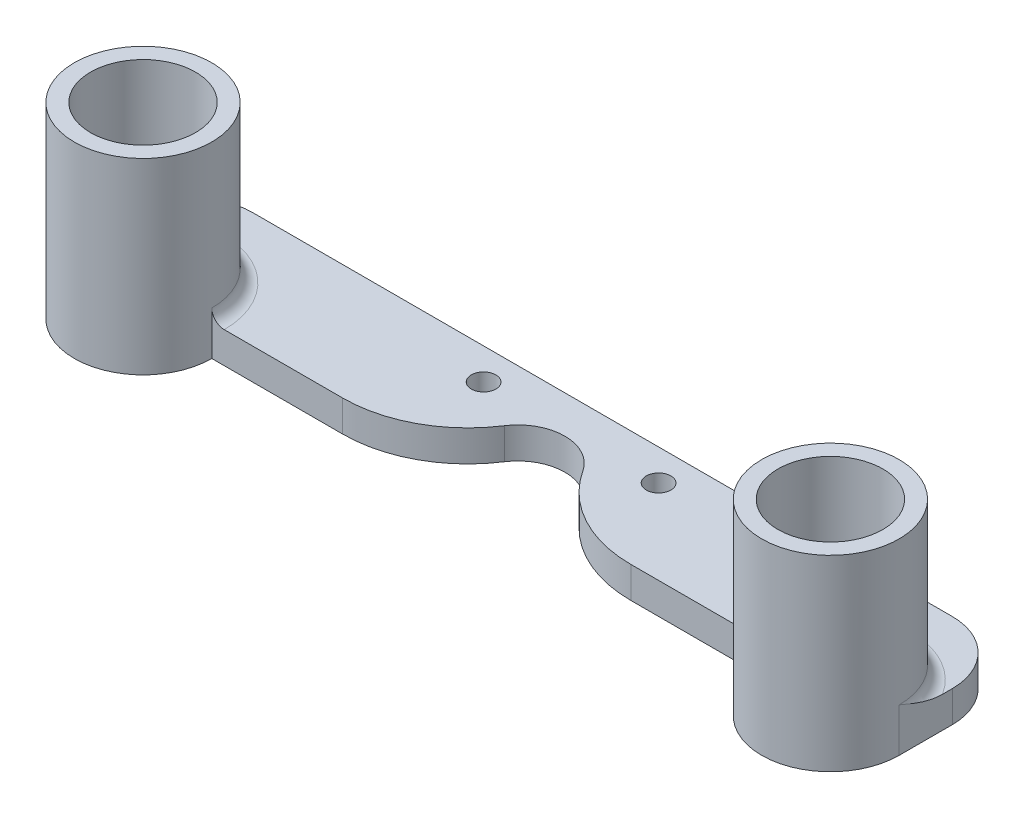
SolidWorks part; units mm, degrees
ref_plane "Front Plane" through (0, 0, 0) normal (0, 0, 1) x (1, 0, 0)
ref_plane "Top Plane" through (0, 0, 0) normal (0, 1, 0) x (1, 0, 0)
ref_plane "Right Plane" through (0, 0, 0) normal (1, 0, 0) x (0, 0, -1)
sketch "Sketch1" plane through (0, 0, 0) normal (0, 1, 0) x (1, 0, 0)
  line L0 (0, 0) -> (30.6893, 0) construction
  line L1 (30.6893, 0) -> (0, 0) construction
  line L2 (0, 0) -> (-18.0912, 0) construction
  line L3 (-81.0707, 0) -> (-54.4628, 0)
  line L5 (-109.0107, 0) -> (-109.0107, 10.795)
  line L6 (-96.3107, 23.495) -> (45.9293, 23.495)
  line L7 (58.6293, 0) -> (58.6293, 10.795)
  line L8 (4.0813, 0) -> (30.6893, 0)
  line L9 (-32.2902, 0) -> (-81.0707, 0) construction
  arc A0 (-109.0107, 0) -> (-81.0707, 0) centre (-95.0407, 0) ccw
  arc A1 (30.6893, 0) -> (58.6293, 0) centre (44.6593, 0) ccw
  circle A2 centre (-95.0407, 0) radius 10.668
  circle A3 centre (44.6593, 0) radius 10.668
  circle A5 centre (-7.4107, 17.145) radius 2.5
  circle A6 centre (-42.9707, 17.145) radius 2.5
  arc A7 (45.9293, 23.495) -> (58.6293, 10.795) centre (45.9293, 10.795) cw
  arc A8 (-109.0107, 10.795) -> (-96.3107, 23.495) centre (-96.3107, 10.795) cw
  arc A9 (-17.2074, 11.5455) -> (-33.174, 11.5455) centre (-25.1907, 6.35) ccw
  arc A10 (-33.174, 11.5455) -> (-54.4628, 0) centre (-54.4628, 25.4) cw
  arc A11 (-17.2074, 11.5455) -> (4.0813, 0) centre (4.0813, 25.4) ccw
  point P24 (-17.9573, 16.7779)
  dimension "D1" = 12.7
  dimension "D2" = 21.336
  dimension "D5" = 19.05
  dimension "D12" = 5
  dimension "D13" = 5
  dimension "D14" = 25.4
  dimension "D15" = 25.4
  dimension "D3" = 13.97
  dimension "D4" = 23.495
  dimension "D6" = 35.56
  dimension "D7" = 17.78
  dimension "D8" = 6.35
  dimension "D9" = 6.35
  dimension "D10" = 139.7
  dimension "D11" = 69.85
extrude "Boss-Extrude1" add sketch "Sketch1" along normal blind 6.35
sketch "Sketch2" plane through (0, 6.35, 0) normal (0, 1, 0) x (1, 0, 0)
  circle A0 centre (-95.0407, 0) radius 13.97
  circle A1 centre (-95.0407, 0) radius 10.668
  circle A2 centre (44.6593, 0) radius 13.97
  circle A3 centre (44.6593, 0) radius 10.668
extrude "Boss-Extrude2" add sketch "Sketch2" along normal blind 31.75
fillet "Fillet1" radius 2.54 2 edges at (-95.0407, 6.35, -13.97) (44.6593, 6.35, -13.97)
